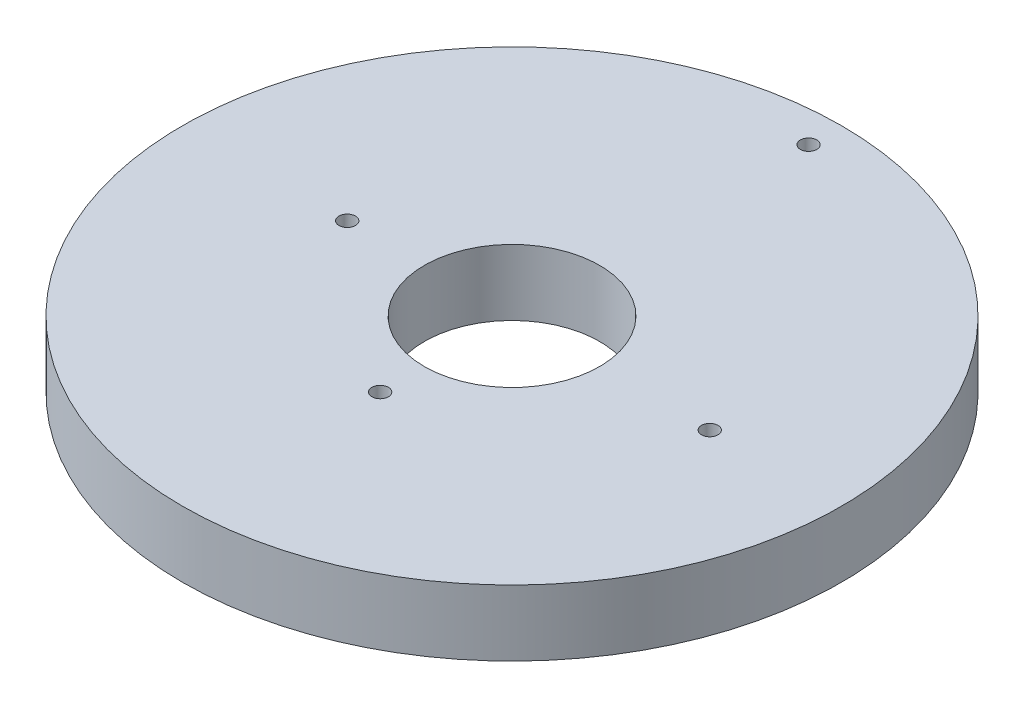
SolidWorks part; units mm, degrees
ref_plane "Front Plane" through (0, 0, 0) normal (0, 0, 1) x (1, 0, 0)
ref_plane "Top Plane" through (0, 0, 0) normal (0, 1, 0) x (1, 0, 0)
ref_plane "Right Plane" through (0, 0, 0) normal (1, 0, 0) x (0, 0, -1)
sketch "Sketch1" plane through (0, 0, 0) normal (0, 1, 0) x (1, 0, 0)
  line L0 (0, -63.5) -> (0, 63.5) construction
  line L1 (-63.5, 0) -> (63.5, 0) construction
  circle A0 centre (0, 0) radius 16.891
  circle A1 centre (0, 0) radius 63.5
  circle A2 centre (0, 57.15) radius 1.5875
  circle A3 centre (38.1, 0) radius 1.5875
  circle A4 centre (-31.75, 0) radius 1.5875
  circle A5 centre (0, -25.4) radius 1.5875
  point P16 (0, 0)
  dimension "D1" = 33.782
  dimension "D2" = 127
  dimension "D3" = 3.175
  dimension "D4" = 3.175
  dimension "D5" = 3.175
  dimension "D6" = 3.175
  dimension "D7" = 57.15
  dimension "D8" = 31.75
  dimension "D9" = 25.4
  dimension "D10" = 38.1
extrude "Boss-Extrude1" add sketch "Sketch1" along normal blind 12.7
